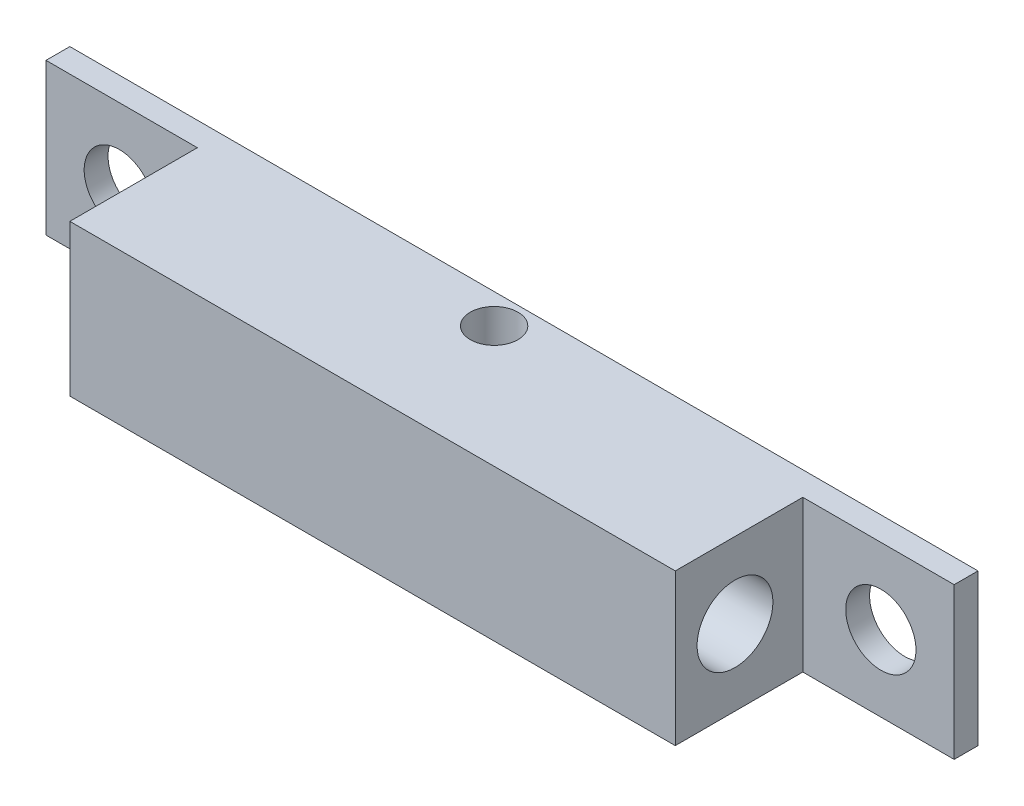
SolidWorks part; units mm, degrees
other "Markup1"
sketch "Sketch4" plane through (-6.35, -10, 15) normal (-0.3542, -0.9351, 0.0128) x (0.9346, -0.3545, -0.0309)
ref_plane "Front Plane" through (0, 0, 0) normal (0, 0, 1) x (1, 0, 0)
ref_plane "Top Plane" through (0, 0, 0) normal (0, 1, 0) x (1, 0, 0)
ref_plane "Right Plane" through (0, 0, 0) normal (1, 0, 0) x (0, 0, -1)
sketch "Sketch1" plane through (0, 0, 0) normal (0, 0, 1) x (1, 0, 0)
  line L1 (0, 0) -> (25.4, 0)
  line L2 (0, 0) -> (0, -6.35)
  line L3 (0, -6.35) -> (25.4, -6.35)
  line L4 (25.4, 0) -> (25.4, -6.35)
  line L5 (0, 0) -> (-6.35, 0)
  line L6 (0, 0) -> (0, -6.35)
  line L7 (0, -6.35) -> (-6.35, -6.35)
  line L8 (-6.35, 0) -> (-6.35, -6.35)
  line L9 (25.4, 0) -> (31.75, 0)
  line L10 (25.4, 0) -> (25.4, -6.35)
  line L11 (25.4, -6.35) -> (31.75, -6.35)
  line L12 (31.75, 0) -> (31.75, -6.35)
  circle A0 centre (-3.275, -3.175) radius 1.4732
  circle A1 centre (28.675, -3.175) radius 1.4732
  circle A2 centre (-3.275, -3.175) radius 2.3241 construction
  circle A3 centre (28.675, -3.175) radius 2.3241 construction
  point P19 (-6.35, -3.175)
  dimension "D1" = 2.9464
  dimension "D10" = 4.6482
  dimension "D11" = 4.6482
  dimension "D2" = 25.4
  dimension "D3" = 6.35
  dimension "D4" = 3.275
  dimension "D5" = 3.275
  dimension "D7" = 3.175
  dimension "D8" = 6.35
  dimension "D9" = 3.175
extrude "Boss-Extrude1" add sketch "Sketch1" along normal blind 1 contours L5 L8 L7 L2 A0 | L12 L9 L4 L11 A1 region at (-0.0898, -3.175, 0) region at (28.575, -0.0898, 0)
extrude "Boss-Extrude2" add sketch "Sketch1<3>" along normal blind 6.35 contours L4 L1 L2 L3 region at (12.7, -3.175, 0)
sketch "Sketch1<3>" plane through (0, 0, 0) normal (0, 0, 1) x (1, 0, 0) same geometry as "Sketch1"
sketch "Sketch2" plane through (0, 0, 0) normal (-1, 0, 0) x (0, 0, 1)
  line L1 (3.8448, 0) -> (3.8448, -6.35) construction
  line L2 (6.35, 0) -> (1, 0) construction
  line L3 (6.35, -6.35) -> (1, -6.35) construction
  line L4 (1, 0) -> (1, -6.35) construction
  circle A0 centre (3.8448, -3.175) radius 1.591
  dimension "D1" = 3.182
  dimension "D2" = 2.8448
  dimension "D3" = 0
  dimension "D4" = 3.175
extrude "Cut-Extrude1" cut sketch "Sketch2" against normal up to surface (25.4 mm away) up to face at (25.4, -3.175, 3.675)
sketch "Sketch3" plane through (0, 0, 0) normal (0, 1, 0) x (1, 0, 0)
  line L0 (0, -6.35) -> (0, -1) construction
  line L2 (-6.35, 0) -> (31.75, 0) construction
  circle A0 centre (12.7, -1.25) radius 1
  dimension "D1" = 2
  dimension "D2" = 12.7
  dimension "D3" = 1.25
extrude "Cut-Extrude2" cut sketch "Sketch3" against normal up to surface (6.35 mm away) contours A0 up to face at (12.7, -6.35, 2.0875)
equation "\"D4@Sketch1\"=(\"D3@Sketch1\")/2+0.1"
equation "\"D5@Sketch1\"=\"D4@Sketch1\""
equation "\"D7@Sketch1\"=\"D8@Sketch1\"/2"
equation "\"D9@Sketch1\"=\"D8@Sketch1\"/2"
